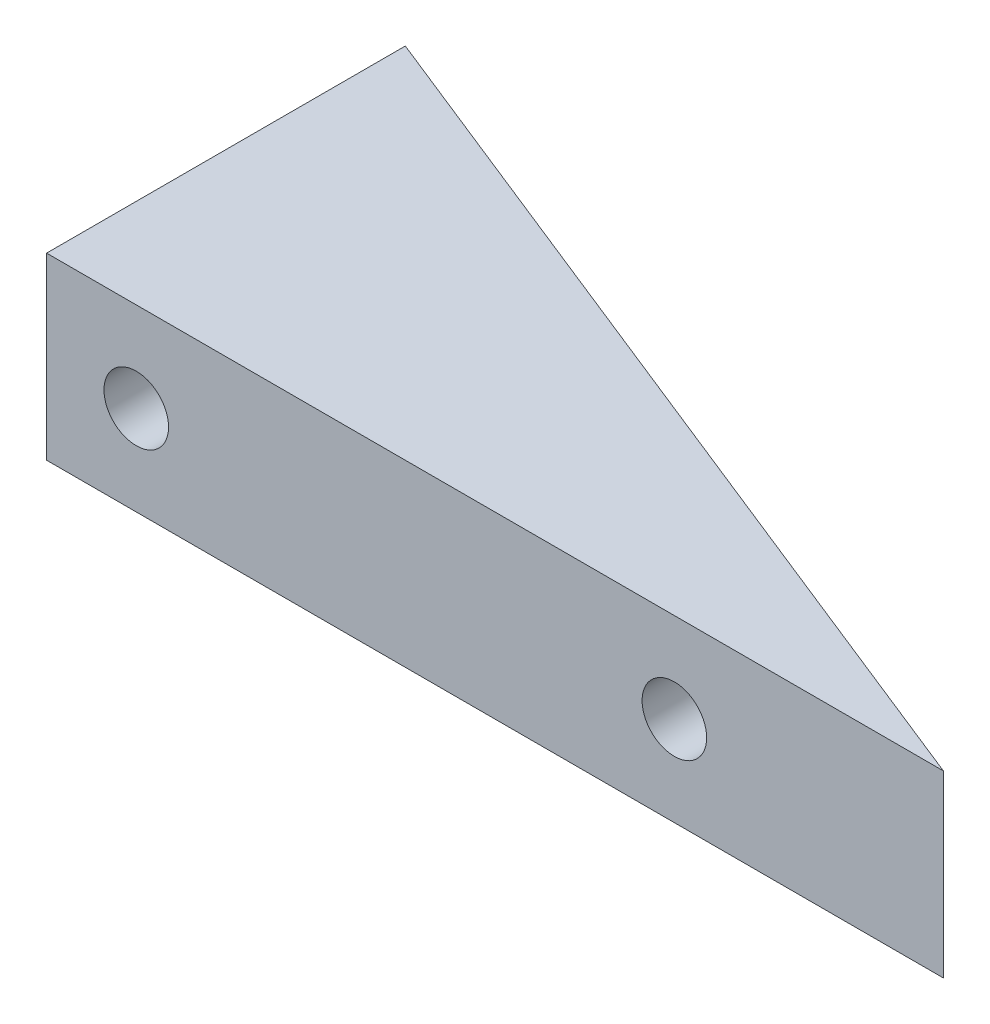
SolidWorks part; units mm, degrees
ref_plane "Front Plane" through (0, 0, 0) normal (0, 0, 1) x (1, 0, 0)
ref_plane "Top Plane" through (0, 0, 0) normal (0, 1, 0) x (1, 0, 0)
ref_plane "Right Plane" through (0, 0, 0) normal (1, 0, 0) x (0, 0, -1)
sketch "Sketch1" plane through (0, 0, 0) normal (0, 1, 0) x (1, 0, 0)
  line L0 (0, 0) -> (0, 25.4)
  line L1 (0, 25.4) -> (63.5, 0)
  line L2 (63.5, 0) -> (0, 0)
  dimension "D1" = 25.4
  dimension "D2" = 63.5
extrude "Boss-Extrude1" add sketch "Sketch1" along normal blind 12.7
ref_plane "Plane1" through (0, 0, -25.4) normal (0, 0, 1) x (1, 0, 0)
sketch "Sketch2" plane through (0, 0, -25.4) normal (0, 0, 1) x (1, 0, 0)
  line L0 (44.45, 6.35) -> (6.35, 6.35) construction
  line L1 (63.5, 12.7) -> (0, 12.7) construction
  line L2 (0, 12.7) -> (0, 0) construction
  circle A0 centre (44.45, 6.35) radius 2.286
  circle A1 centre (6.35, 6.35) radius 2.286
  dimension "D1" = 4.572
  dimension "D2" = 4.572
  dimension "D4" = 6.35
  dimension "D3" = 6.35
  dimension "D5" = 38.1
extrude "Cut-Extrude1" cut sketch "Sketch2" along normal through all
